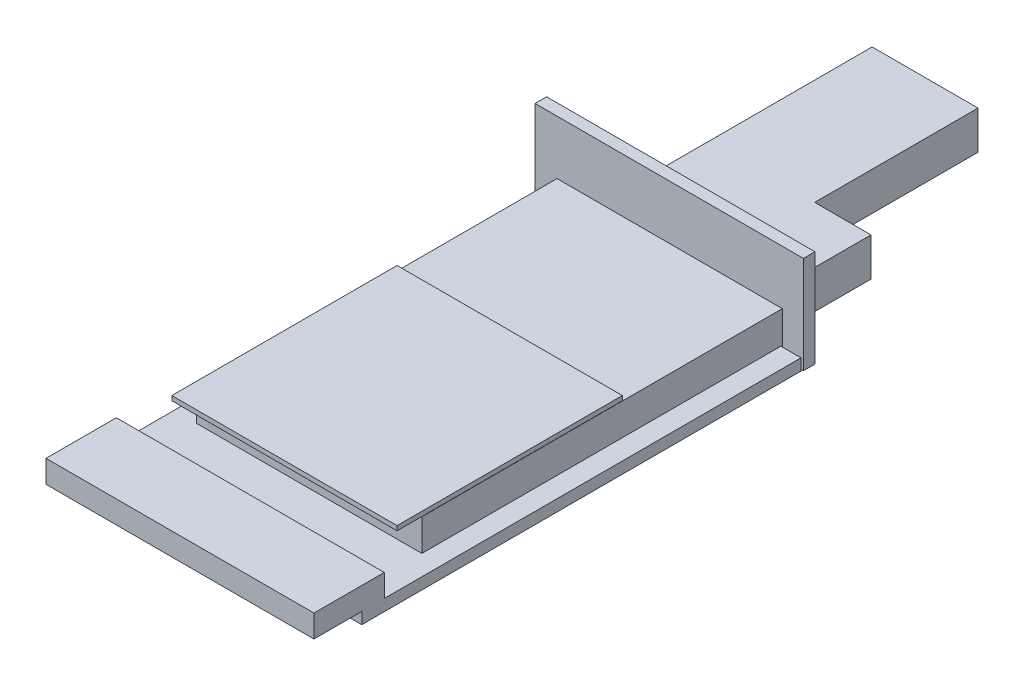
SolidWorks part; units mm, degrees
ref_plane "Front Plane" through (0, 0, 0) normal (0, 0, 1) x (1, 0, 0)
ref_plane "Top Plane" through (0, 0, 0) normal (0, 1, 0) x (1, 0, 0)
ref_plane "Right Plane" through (0, 0, 0) normal (1, 0, 0) x (0, 0, -1)
sketch "Sketch3" plane through (0, 0, 0) normal (0, 1, 0) x (1, 0, 0)
  line L0 (-49.0663, -344.8689) -> (-49.0663, -332.1689)
  line L11 (-48.7979, -96.4112) -> (102.5042, -96.4112)
  line L12 (-48.7979, -96.4112) -> (-48.7979, -89.8961)
  line L13 (-48.7979, -89.8961) -> (102.5042, -89.8961)
  line L14 (102.5042, -96.4112) -> (102.5042, -89.8961)
  line L49 (-25.4693, -319.4839) -> (-49.0663, -319.4839)
  line L51 (-49.0663, -97.2339) -> (101.9863, -97.2339)
  line L52 (-49.0663, -97.2339) -> (-49.0663, -344.8689)
  line L53 (-49.0663, -344.8689) -> (101.9863, -344.8689)
  line L54 (101.9863, -97.2339) -> (101.9863, -344.8689)
  line L55 (-49.0663, -97.2339) -> (-36.3929, -96.4112)
  line L56 (-49.0663, -332.1689) -> (101.9863, -332.1689)
  line L57 (-49.0663, -332.1689) -> (-49.0663, -371.8169)
  line L58 (-49.0663, -371.8169) -> (101.9863, -371.8169)
  line L59 (101.9863, -332.1689) -> (101.9863, -371.8169)
  line L60 (-36.3929, -96.4112) -> (-36.3929, -186.5812)
  line L61 (-36.3929, -96.4112) -> (90.6071, -96.4112)
  line L62 (-36.3929, -96.4112) -> (-36.3929, -299.6112)
  line L63 (-36.3929, -299.6112) -> (90.6071, -299.6112)
  line L64 (90.6071, -96.4112) -> (90.6071, -299.6112)
  line L65 (-8.1579, -89.8961) -> (51.5321, -89.8961)
  line L66 (-36.3929, -186.5812) -> (90.6071, -186.5812)
  line L67 (-36.3929, -186.5812) -> (-36.3929, -313.5812)
  line L68 (-36.3929, -313.5812) -> (90.6071, -313.5812)
  line L69 (90.6071, -186.5812) -> (90.6071, -313.5812)
  line L70 (-8.1579, -89.8961) -> (-8.1579, 52.9789)
  line L71 (-8.1579, 52.9789) -> (51.5321, 52.9789)
  line L72 (51.5321, -89.8961) -> (51.5321, 52.9789)
  line L73 (51.5321, -89.8961) -> (83.2821, -89.8961)
  line L74 (51.5321, -89.8961) -> (51.5321, -39.0961)
  line L75 (51.5321, -39.0961) -> (83.2821, -39.0961)
  line L76 (83.2821, -89.8961) -> (83.2821, -39.0961)
  dimension "D4" = 12.7
  dimension "D5" = 6.5151
  dimension "D6" = 222.25
  dimension "D7" = 203.2
  dimension "D8" = 127
extrude "Boss-Extrude1" add sketch "Sketch3" along normal blind 54.864 contours L11 L14 L13 L12
extrude "Boss-Extrude4" add sketch "Sketch3<13>" along normal blind 6.477 separate body contours L53 L54 L51 L52
sketch "Sketch3<13>" plane through (0, 0, 0) normal (0, 1, 0) x (1, 0, 0) same geometry as "Sketch3"
extrude "Boss-Extrude5" add sketch "Sketch3<14>" along normal blind 12.7 from offset 6.477 contours L57 L58 L59 L56
sketch "Sketch3<14>" plane through (0, 0, 0) normal (0, 1, 0) x (1, 0, 0) same geometry as "Sketch3"
extrude "Boss-Extrude6" add sketch "Sketch3<15>" along normal blind 24.384 contours L62 L63 L64 L61
sketch "Sketch3<15>" plane through (0, 0, 0) normal (0, 1, 0) x (1, 0, 0) same geometry as "Sketch3"
extrude "Boss-Extrude7" add sketch "Sketch3<16>" along normal blind 2.54 from offset 24.511 separate body contours L67 L68 L69 L66
sketch "Sketch3<16>" plane through (0, 0, 0) normal (0, 1, 0) x (1, 0, 0) same geometry as "Sketch3"
extrude "Boss-Extrude12" add sketch "Sketch3<22>" along normal blind 21.59 from offset 6.477 contours L73 L76 L75 L74
sketch "Sketch3<22>" plane through (0, 0, 0) normal (0, 1, 0) x (1, 0, 0) same geometry as "Sketch3"
extrude "Boss-Extrude13" add sketch "Sketch3<23>" along normal blind 21.59 from offset 6.477 contours L65 L70 L71 L72
sketch "Sketch3<23>" plane through (0, 0, 0) normal (0, 1, 0) x (1, 0, 0) same geometry as "Sketch3"
sketch "Sketch6" plane through (0, 54.864, 0) normal (0, 1, 0) x (1, 0, 0)
ref_plane "Plane1" through (102.5042, 54.864, 89.8961) normal (0, 0, -1) x (-1, 0, 0)
